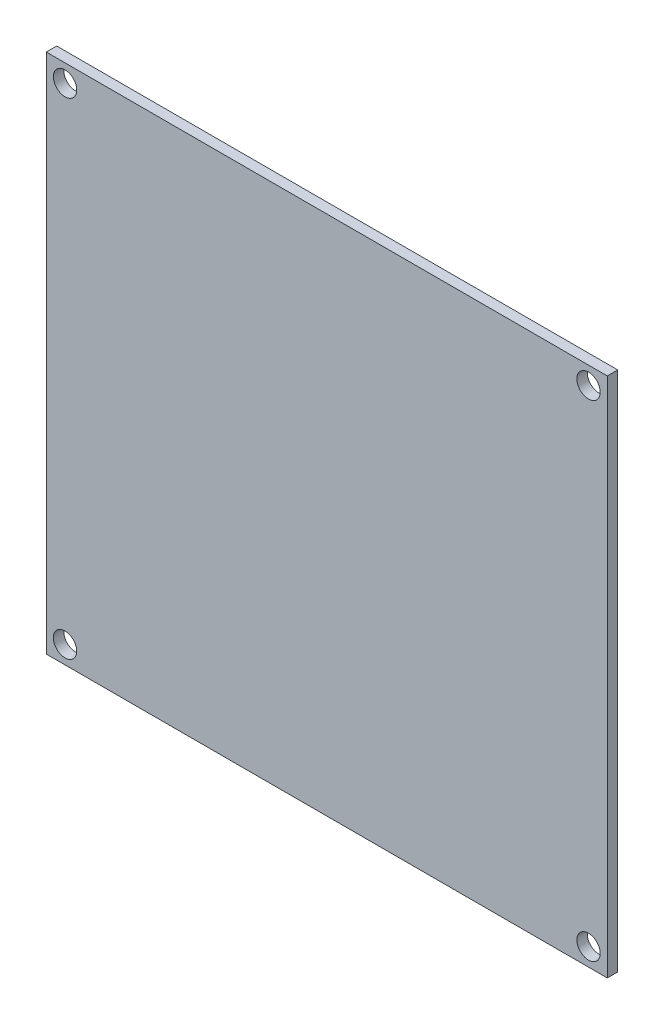
SolidWorks part; units mm, degrees
ref_plane "Front Plane" through (0, 0, 0) normal (0, 0, 1) x (1, 0, 0)
ref_plane "Top Plane" through (0, 0, 0) normal (0, 1, 0) x (1, 0, 0)
ref_plane "Right Plane" through (0, 0, 0) normal (1, 0, 0) x (0, 0, -1)
sketch "Sketch1" plane through (0, 0, 0) normal (0, 0, 1) x (1, 0, 0)
  line L0 (-63.754, 63.5) -> (-63.754, 59.182) construction
  line L1 (68.326, -63.5) -> (-68.326, -63.5)
  line L2 (68.326, -63.5) -> (68.326, 63.5)
  line L3 (68.326, 63.5) -> (-68.326, 63.5)
  line L4 (-68.326, -63.5) -> (-68.326, 63.5)
  line L5 (68.326, -63.5) -> (-68.326, 63.5) construction
  line L6 (68.326, 63.5) -> (-68.326, -63.5) construction
  line L7 (-63.754, 59.182) -> (-68.326, 59.182) construction
  line L8 (0, -55) -> (0, 55) construction
  line L9 (55, 0) -> (-55, 0) construction
  circle A0 centre (-63.754, 59.182) radius 2.8448
  circle A1 centre (63.754, 59.182) radius 2.8448
  circle A2 centre (63.754, -59.182) radius 2.8448
  circle A3 centre (-63.754, -59.182) radius 2.8448
  point P0 (0, 0)
extrude "Boss-Extrude1" add sketch "Sketch1" along normal blind 2.54 contours L3 L4 L1 L2
extrude "Cut-Extrude3" cut sketch "Sketch1<5>" along normal blind 30.48 flip side to cut
sketch "Sketch1<5>" plane through (0, 0, 0) normal (0, 0, 1) x (1, 0, 0) same geometry as "Sketch1"
